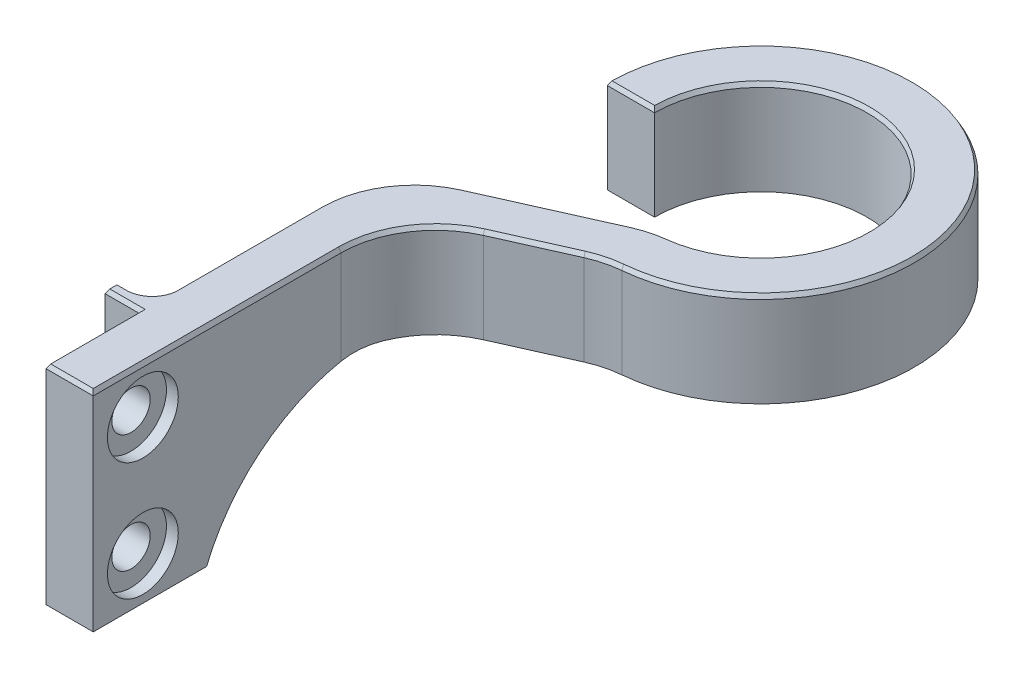
SolidWorks part; units mm, degrees
ref_plane "Front Plane" through (0, 0, 0) normal (0, 0, 1) x (1, 0, 0)
ref_plane "Top Plane" through (0, 0, 0) normal (0, 1, 0) x (1, 0, 0)
ref_plane "Right Plane" through (0, 0, 0) normal (1, 0, 0) x (0, 0, -1)
sketch "Sketch1" plane through (0, 0, 0) normal (0, 1, 0) x (1, 0, 0)
  line L1 (-16, -16.1332) -> (-16, -44.5201)
  line L2 (-16, -44.5201) -> (-12, -44.5201)
  line L3 (-9, 0) -> (-13, 0)
  line L4 (-12, -44.5201) -> (-12, -18.3499)
  line L5 (-12, -18.3499) -> (0, -13)
  line L6 (-16, -16.1332) -> (0, -9)
  arc A0 (0, -9) -> (-9, 0) centre (0, 0) ccw
  arc A1 (0, -13) -> (-13, 0) centre (0, 0) ccw
  dimension "D1" = 18
  dimension "D2" = 4
  dimension "D4" = 4
extrude "Boss-Extrude1" add sketch "Sketch1" along normal blind 8
sketch "Sketch2" plane through (-16, 0, 0) normal (-1, 0, 0) x (0, 0, 1)
  line L0 (44.5201, 0) -> (44.5201, -9.6498)
  line L1 (44.5201, 0) -> (18.3499, 0) construction
  line L2 (44.5201, -9.6498) -> (34.927, -9.6498)
  line L3 (44.5201, 0) -> (20.5201, 0)
  line L4 (44.5201, 8) -> (44.5201, 0) construction
  line L5 (16.1332, 0) -> (44.5201, 0) construction
  arc A0 (34.927, -9.6498) -> (20.5201, 0) centre (20.5201, -15.5794) ccw
extrude "Boss-Extrude2" add sketch "Sketch2" against normal blind 4
fillet "Fillet1" radius 8 4 edges at (0, 4, 9) (0, 4, 13) (-16, 4, 16.1332) (-12, 4, 18.3499)
sketch "Sketch3" plane through (-12, 0, 0) normal (1, 0, 0) x (0, 0, -1)
  circle A0 centre (-40.3201, 4) radius 1.625
  circle A1 centre (-40.3201, -6) radius 1.625
  dimension "D1" = 3.25
extrude "Cut-Extrude1" cut sketch "Sketch3" against normal through all
sketch "Sketch4" plane through (-12, 0, 0) normal (1, 0, 0) x (0, 0, -1)
  circle A0 centre (-40.3201, 4) radius 3
  circle A1 centre (-40.3201, -6) radius 3
  dimension "D2" = 6
extrude "Cut-Extrude2" cut sketch "Sketch4" against normal blind 1
sketch "Sketch5" plane through (-16, 0, 0) normal (-1, 0, 0) x (0, 0, 1)
  line L0 (21.3256, 8) -> (44.5201, 8) construction
  line L1 (36.5201, 8) -> (35.5201, 8)
  line L2 (36.5201, 8) -> (36.5201, -9.6498)
  line L3 (36.5201, -9.6498) -> (35.5201, -9.6498)
  line L4 (35.5201, 8) -> (35.5201, -9.6498)
  line L6 (34.927, -9.6498) -> (44.5201, -9.6498) construction
  dimension "D1" = 1
extrude "Boss-Extrude3" add sketch "Sketch5" along normal blind 3
fillet "Fillet2" radius 2 1 edges at (-16, -0.8249, 35.5201)
chamfer "Chamfer1" distance 0.2 angle 60 17 edges at (-19, 8, 36.0201) (-17.5, 8, 36.5201) (-16, 8, 40.5201) (-14, 8, 44.5201) (-11, 8, 0) (8.7679, 8, -9.5981) (-0.1222, 8, 13.1728) (-12, 8, 34.0312) (-4.3102, 8, 14.9216) (-10.7104, 8, 19.1869) (5.9867, 8, -6.7201) (-0.1576, 8, 9.1713) (-18.5, 8, 35.5201) (-6.2797, 8, 11.7996) (-16.5858, 8, 34.9343) (-16, 8, 27.4229) (-14.7104, 8, 16.9702) first distance on face at (-9.5366, 8, 21.0819)
